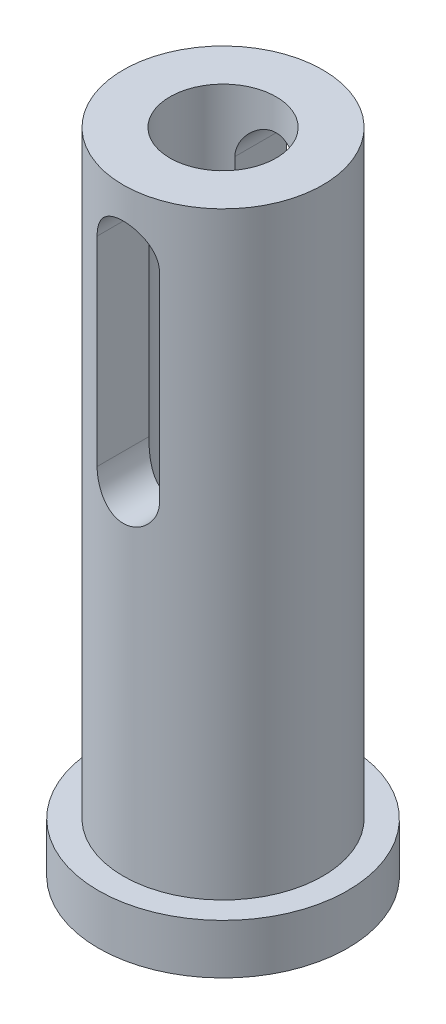
SolidWorks part; units mm, degrees
ref_plane "Front Plane" through (0, 0, 0) normal (0, 0, 1) x (1, 0, 0)
ref_plane "Top Plane" through (0, 0, 0) normal (0, 1, 0) x (1, 0, 0)
ref_plane "Right Plane" through (0, 0, 0) normal (1, 0, 0) x (0, 0, -1)
sketch "Sketch1" plane through (0, 0, 0) normal (0, 1, 0) x (1, 0, 0)
  circle A0 centre (0, 0) radius 3.175
  dimension "D1" = 6.35
extrude "Boss-Extrude1" add sketch "Sketch1" along normal blind 1.27
sketch "Sketch2" plane through (0, 1.27, 0) normal (0, 1, 0) x (1, 0, 0)
  circle A0 centre (0, 0) radius 2.54
  dimension "D1" = 5.08
extrude "Boss-Extrude2" add sketch "Sketch2" along normal blind 15.24
hole_wizard "Tap Drill for #6-32 Tap1" positions "Sketch5" profile "Sketch4" hole size "#6-32" standard "ANSI Inch" end condition through all
sketch "Sketch5" plane through (0, 16.51, 0) normal (0, 1, 0) x (1, 0, 0)
  point P0 (0, 0)
sketch "Sketch4" plane through (0, 16.51, 0) normal (1, 0, 0) x (0, 0, 1)
  line L0 (0, 0) -> (0, 16.51)
  line L1 (0, 16.51) -> (1.3525, 16.51)
  line L2 (1.3525, 16.51) -> (1.3525, 0)
  line L5 (1.3525, 0) -> (0, 0)
  line L11 (0, -6.35) -> (0, 107.95) construction
  dimension "Thru Hole Dia." = 2.7051
  dimension "Thru Hole Depth" = 16.51
sketch "Sketch6" plane through (0, 0, 0) normal (0, 0, 1) x (1, 0, 0)
  line L0 (0, 14.9225) -> (0, 9.8425) construction
  line L1 (0.7937, 14.9225) -> (0.7938, 9.8425)
  line L2 (-0.7938, 14.9225) -> (-0.7937, 9.8425)
  line L3 (1.3525, 16.51) -> (-1.3525, 16.51) construction
  arc A0 (0.7937, 14.9225) -> (-0.7938, 14.9225) centre (0, 14.9225) ccw
  arc A1 (-0.7937, 9.8425) -> (0.7938, 9.8425) centre (0, 9.8425) ccw
  point P3 (0, 12.3825)
  dimension "D1" = 1.5875
  dimension "D2" = 5.08
  dimension "D3" = 1.5875
extrude "Cut-Extrude1" cut sketch "Sketch6" against normal through all both and the other way through all
